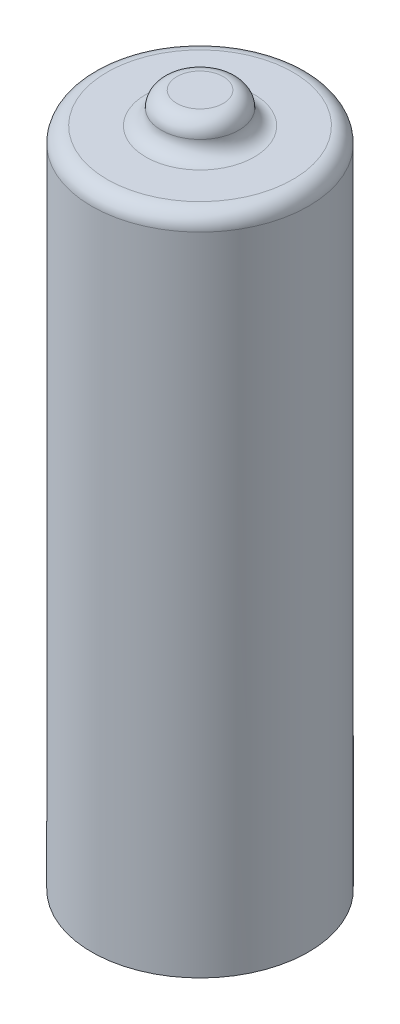
SolidWorks part; units mm, degrees
ref_plane "Front Plane" through (0, 0, 0) normal (0, 0, 1) x (1, 0, 0)
ref_plane "Top Plane" through (0, 0, 0) normal (0, 1, 0) x (1, 0, 0)
ref_plane "Right Plane" through (0, 0, 0) normal (1, 0, 0) x (0, 0, -1)
sketch "Sketch1" plane through (0, 0, 0) normal (0, 1, 0) x (1, 0, 0)
  circle A0 centre (0, 0) radius 7
  dimension "D1" = 14
extrude "Boss-Extrude1" add sketch "Sketch1" along normal blind 42.7
sketch "Sketch3" plane through (0, 0, 0) normal (0, -1, 0) x (1, 0, 0)
  circle A0 centre (0, 0) radius 6
  circle A1 centre (0, 0) radius 7 construction
  dimension "D1" = 1
extrude "Cut-Extrude1" cut sketch "Sketch3" against normal blind 1
sketch "Sketch2" plane through (0, 42.7, 0) normal (0, 1, 0) x (1, 0, 0)
  circle A0 centre (0, 0) radius 2.5
  dimension "D1" = 5
extrude "Boss-Extrude2" add sketch "Sketch2" along normal blind 2 and the other way up to surface (42.7 mm away) other way up to face at (0, 0, -6)
fillet "Fillet2" radius 1 1 edges at (0, 1, -2.5)
fillet "Fillet4" radius 1 3 edges at (0, 44.7, 2.5) (0, 42.7, 2.5) (0, 42.7, 7)
